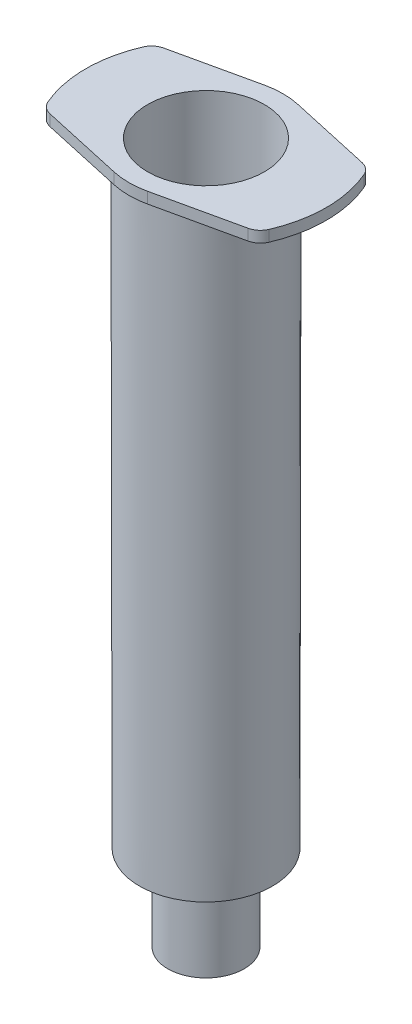
SolidWorks part; units mm, degrees
ref_plane "Front" through (0, 0, 0) normal (0, 0, 1) x (1, 0, 0)
ref_plane "Top" through (0, 0, 0) normal (0, 1, 0) x (1, 0, 0)
ref_plane "Right" through (0, 0, 0) normal (1, 0, 0) x (0, 0, -1)
sketch "Sketch1" plane through (0, 0, 0) normal (0, 0, 1) x (1, 0, 0)
  line L0 (0, 0) -> (0, 86.37) construction
  line L1 (8.3, 86.37) -> (8.2, 10.5763)
  line L2 (8.2, 10.5763) -> (4.71, 8.87)
  line L3 (4.71, 8.87) -> (4.71, 0)
  line L4 (4.71, 0) -> (3.96, 0)
  line L5 (3.96, 0) -> (3.96, 4.3911)
  line L6 (3.96, 4.3911) -> (2, 4.3911)
  line L7 (2, 4.3911) -> (2, 0)
  line L8 (2, 0) -> (1, 0)
  line L9 (0, 86.37) -> (8.3, 86.37) construction
  line L10 (1, 0) -> (1, 8.1693)
  line L11 (8.3, 86.37) -> (7.2, 86.37)
  line L12 (7.2, 86.37) -> (7.2, 11.2005)
  line L13 (7.2, 11.2005) -> (1, 8.1693)
  dimension "D2" = 86.37
  dimension "D3" = 16.4
  dimension "D4" = 77.5
  dimension "D5" = 9.42
  dimension "D6" = 0.75
  dimension "D7" = 4
  dimension "D8" = 1
  dimension "D9" = 14.4
  dimension "D10" = 1
  dimension "D11" = 16.6
revolve "Revolve1" add sketch "Sketch1" angle 360 about L0
sketch "Sketch2" plane through (0, 86.37, 0) normal (0, 1, 0) x (1, 0, 0)
  line L0 (0, 0) -> (14.835, 0) construction
  line L1 (14.835, 3.3192) -> (14.835, -3.3192) construction
  line L2 (0, 0) -> (0, 11.561) construction
  line L3 (-14.2552, 0.1088) -> (15.3363, -1.7529) construction
  line L4 (2.0562, 9.2748) -> (13.1803, 6.8087)
  line L5 (-2.0562, 9.2748) -> (-13.1803, 6.8087)
  line L6 (-2.0562, -9.2748) -> (-13.1803, -6.8087)
  line L7 (2.0562, -9.2748) -> (13.1803, -6.8087)
  circle A0 centre (0, 0) radius 9.5 construction
  circle A1 centre (0, 0) radius 14.835 construction
  arc A2 (13.1803, 6.8087) -> (13.1803, -6.8087) centre (0, 0) cw
  arc A3 (-13.1803, 6.8087) -> (-13.1803, -6.8087) centre (0, 0) ccw
  arc A4 (-2.0562, 9.2748) -> (2.0562, 9.2748) centre (0, 0) cw
  arc A5 (2.0562, -9.2748) -> (-2.0562, -9.2748) centre (0, 0) cw
  point P5 (14.835, 0)
  dimension "D2" = 19
  dimension "D3" = 29.65
  dimension "D1" = 14.835
  dimension "D4" = 77.5
extrude "Boss-Extrude2" add sketch "Sketch2" against normal blind 1.37
fillet "Fillet1" radius 2 4 edges at (13.1803, 85.685, 6.8087) (-13.1803, 85.685, 6.8087) (-13.1803, 85.685, -6.8087) (13.1803, 85.685, -6.8087)
sketch "Sketch3" plane through (0, 86.37, 0) normal (0, 1, 0) x (1, 0, 0)
  circle A0 centre (0, 0) radius 7.2
  circle A1 centre (0, 0) radius 7.2 construction
extrude "Cut-Extrude1" cut sketch "Sketch3" against normal up to next
